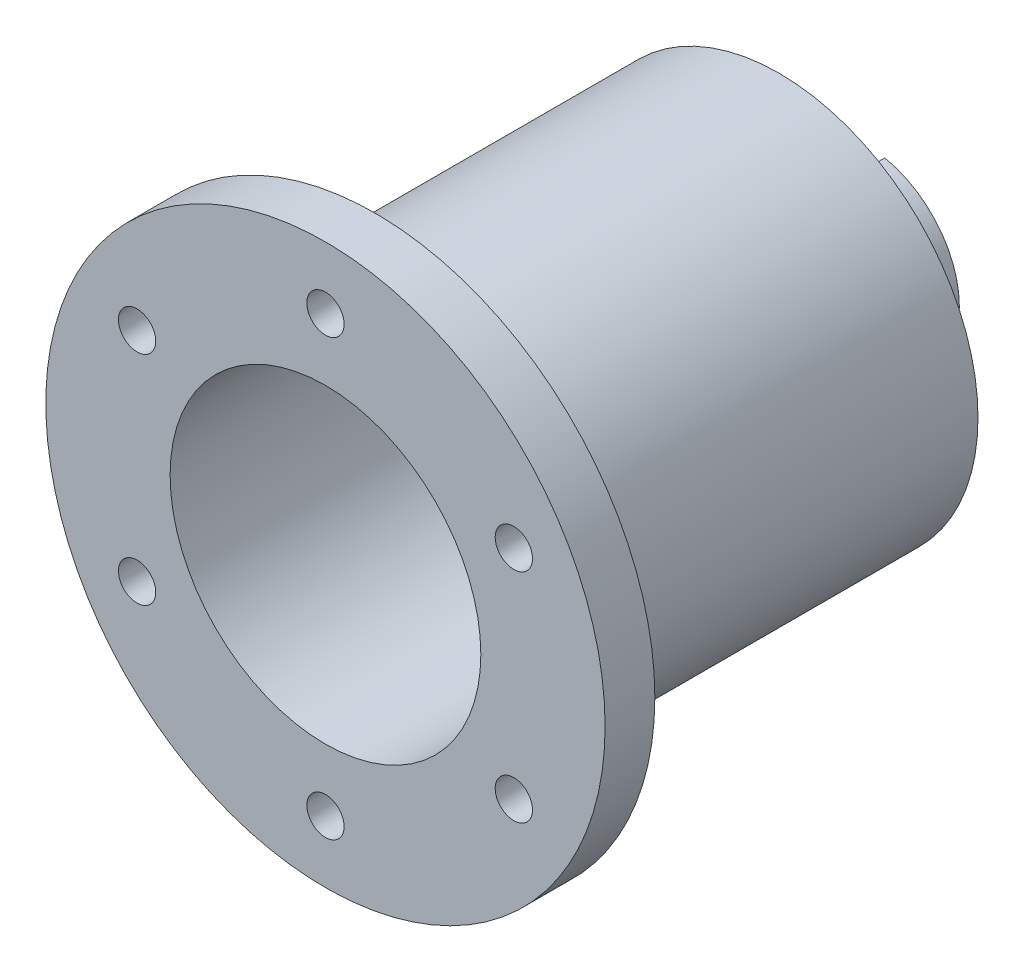
SolidWorks part; units mm, degrees
material "3.1325 (EN-AW 2017A)"
ref_plane "Płaszczyzna przednia" through (0, 0, 0) normal (0, 0, 1) x (1, 0, 0)
ref_plane "Płaszczyzna górna" through (0, 0, 0) normal (0, 1, 0) x (1, 0, 0)
ref_plane "Płaszczyzna prawa" through (0, 0, 0) normal (1, 0, 0) x (0, 0, -1)
sketch "Szkic1" plane through (0, 0, 0) normal (0, 0, 1) x (1, 0, 0)
  circle A0 centre (0, 0) radius 45
  circle A1 centre (0, 0) radius 35 construction
  circle A2 centre (0, 35) radius 3
  circle A3 centre (-30.3109, 17.5) radius 3
  circle A4 centre (30.3109, -17.5) radius 3
  circle A5 centre (30.3109, 17.5) radius 3
  circle A6 centre (0, 0) radius 35 construction
  circle A7 centre (-30.3109, -17.5) radius 3
  circle A8 centre (0, -35) radius 3
  circle A9 centre (0, 0) radius 35 construction
  point P20 (0, 0)
  dimension "D1" = 90
  dimension "D2" = 6
  dimension "D3" = 35
  dimension "D5" = 35
  dimension "D4" = 3
extrude "Dodanie-wyciągnięcie1" add sketch "Szkic1" along normal blind 8
sketch "Szkic2" plane through (0, 0, 0) normal (0, 0, -1) x (-1, 0, 0)
  circle A0 centre (0, 0) radius 32
  dimension "D1" = 64
extrude "Dodanie-wyciągnięcie2" add sketch "Szkic2" along normal blind 65
sketch "Szkic3" plane through (0, 0, -65) normal (0, 0, -1) x (-1, 0, 0)
  circle A0 centre (0, 0) radius 15
  dimension "D1" = 30
extrude "Dodanie-wyciągnięcie3" add sketch "Szkic3" along normal blind 14
sketch "Szkic4" plane through (0, 0, -79) normal (0, 0, -1) x (-1, 0, 0)
  circle A0 centre (0, 0) radius 10
  dimension "D1" = 20
extrude "Wytnij-wyciągnięcie1" cut sketch "Szkic4" against normal blind 96
sketch "Szkic5" plane through (0, 0, 8) normal (0, 0, 1) x (1, 0, 0)
  circle A0 centre (0, 0) radius 25
  dimension "D1" = 50
extrude "Wytnij-wyciągnięcie2" cut sketch "Szkic5" against normal blind 65
sketch "Szkic6" plane through (0, 0, 0) normal (0, 1, 0) x (1, 0, 0)
  line L0 (0, 88.3296) -> (0, 55.3408) construction
  line L1 (-3, 85.59) -> (3, 85.59)
  line L2 (-3, 85.59) -> (-3, 68)
  line L4 (3, 85.59) -> (3, 68)
  line L6 (32, 65) -> (-32, 65) construction
  arc A0 (-3, 68) -> (3, 68) centre (0, 68) ccw
  point P7 (0, 85.59)
  dimension "D1" = 6
extrude "Wytnij-wyciągnięcie3" cut sketch "Szkic6" against normal blind 19 and the other way blind 19
